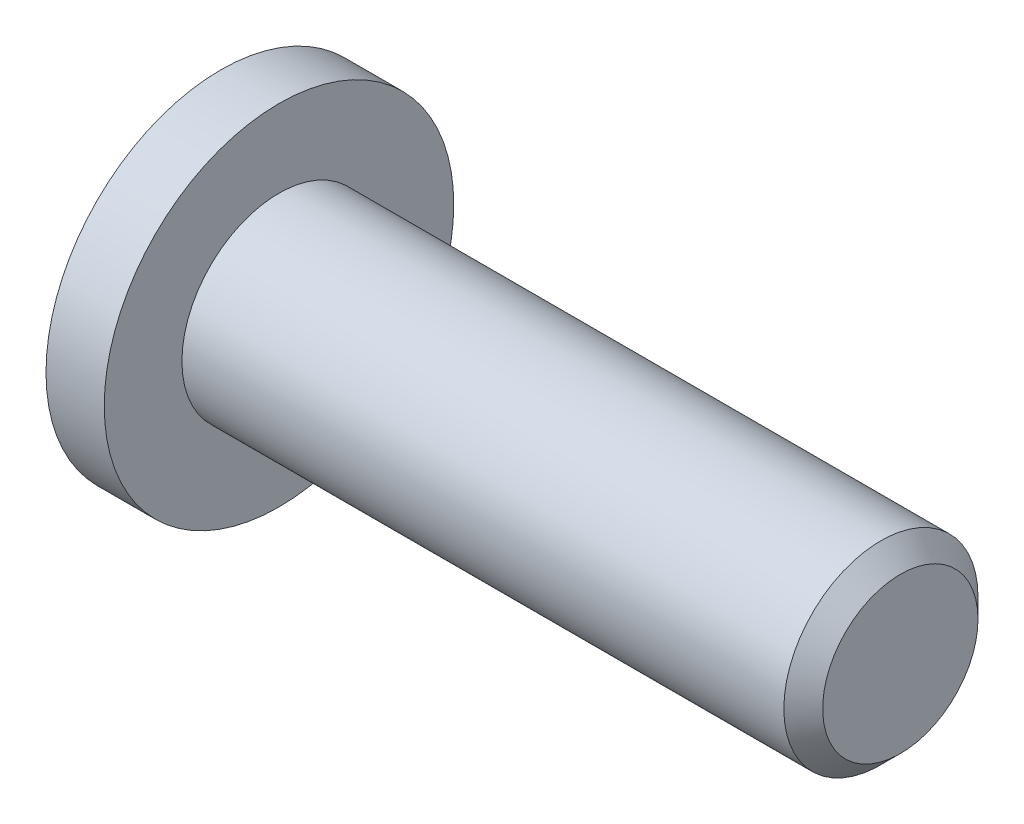
SolidWorks part; units mm, degrees
material "AISI 304"
ref_plane "Front Plane" through (0, 0, 0) normal (0, 0, 1) x (1, 0, 0)
ref_plane "Top Plane" through (0, 0, 0) normal (0, 1, 0) x (1, 0, 0)
ref_plane "Right Plane" through (0, 0, 0) normal (1, 0, 0) x (0, 0, -1)
sketch "Sketch1" plane through (0, 0, 0) normal (1, 0, 0) x (0, 0, -1)
  circle A0 centre (0, 0) radius 4.5
  dimension "D1" = 9
extrude "Head" add sketch "Sketch1" along normal blind 1.5
sketch "Sketch2" plane through (1.5, 0, 0) normal (1, 0, 0) x (0, 0, -1)
  circle A0 centre (0, 0) radius 2.5
  dimension "D1" = 5
extrude "Body" add sketch "Sketch2" along normal blind 16
cosmetic thread "Cosmetic Thread2" parameters "D1"=28, "D2"=4.11
sketch "Sketch3" plane through (0, 0, 0) normal (-1, 0, 0) x (0, 0, 1)
  line L1 (0, 1.7321) -> (-1.5, 0.866)
  line L2 (-1.5, 0.866) -> (-1.5, -0.866)
  line L3 (-1.5, -0.866) -> (0, -1.7321)
  line L4 (0, -1.7321) -> (1.5, -0.866)
  line L5 (1.5, -0.866) -> (1.5, 0.866)
  line L6 (1.5, 0.866) -> (0, 1.7321)
  circle A0 centre (0, 0) radius 1.5 construction
  dimension "D1" = 3
extrude "Drive" cut sketch "Sketch3" against normal blind 3
chamfer "Chamfer1" distance 0.5 angle 45 1 edges at (17.5, 0, -2.5)
